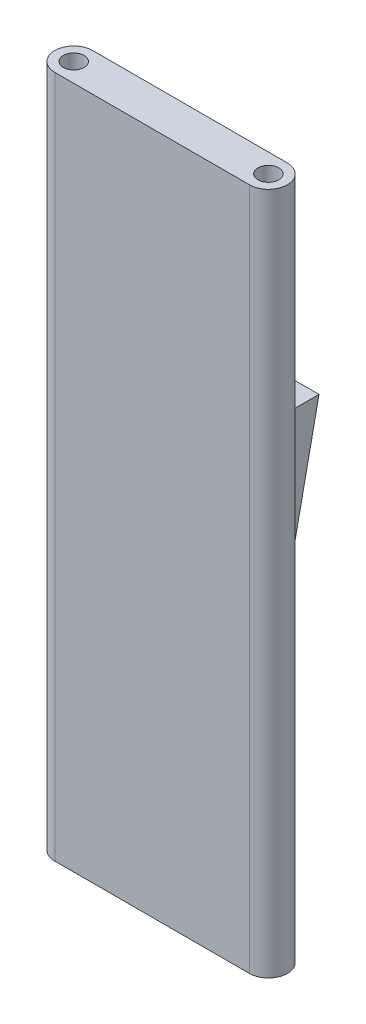
SolidWorks part; units mm, degrees
ref_plane "Front Plane" through (0, 0, 0) normal (0, 0, 1) x (1, 0, 0)
ref_plane "Top Plane" through (0, 0, 0) normal (0, 1, 0) x (1, 0, 0)
ref_plane "Right Plane" through (0, 0, 0) normal (1, 0, 0) x (0, 0, -1)
sketch "Sketch1" plane through (0, 0, 0) normal (0, 1, 0) x (1, 0, 0)
  line L0 (-28.5, 0) -> (28.5, 0) construction
  line L1 (-28.5, 0) -> (28.5, 0) construction
  line L2 (-28.5, 5.55) -> (28.5, 5.55)
  line L3 (-28.5, -5.55) -> (28.5, -5.55)
  circle A0 centre (-28.5, 0) radius 3.05
  circle A1 centre (28.5, 0) radius 3.05
  arc A2 (-28.5, 5.55) -> (-28.5, -5.55) centre (-28.5, 0) ccw
  arc A3 (28.5, -5.55) -> (28.5, 5.55) centre (28.5, 0) ccw
  point P4 (0, 0)
  dimension "D1" = 6.1
  dimension "D2" = 2.5
  dimension "D3" = 57
extrude "Boss-Extrude1" add sketch "Sketch1" along normal mid plane 200
sketch "Sketch2" plane through (0, 0, 0) normal (1, 0, 0) x (0, 0, -1)
  line L0 (5.55, 36.6649) -> (5.55, -0.5321)
  line L1 (5.55, 100) -> (5.55, -100) construction
  line L2 (5.55, -0.5321) -> (7.05, -0.5321)
  line L3 (7.05, -0.5321) -> (14.8208, 36.6649)
  line L4 (14.8208, 36.6649) -> (5.55, 36.6649)
  dimension "D1" = 11.8
  dimension "D2" = 38
  dimension "D3" = 1.5
extrude "Boss-Extrude2" add sketch "Sketch2" along normal up to vertex (28.5 mm away) and the other way up to vertex (28.5 mm away) up to point (28.5, 100, -5.55) other way up to point (-28.5, 100, -5.55)
sketch "Sketch3" plane through (0, -1.4335, -6.8617) normal (0, -0.2045, -0.9789) x (-1, 0, 0)
  line L0 (-14, 33.9209) -> (14, 5.9209) construction
  line L1 (0, 11.204) -> (0, -11.204) construction
  line L3 (-28.5, 0.9209) -> (-28.5, 38.9209) construction
  circle A0 centre (-14, 33.9209) radius 1.5
  circle A1 centre (-14, 5.9209) radius 1.5
  circle A2 centre (14, 33.9209) radius 1.5
  circle A3 centre (14, 5.9209) radius 1.5
  circle A4 centre (-14, 33.9209) radius 2.5
  circle A5 centre (14, 33.9209) radius 2.5
  circle A6 centre (14, 5.9209) radius 2.5
  circle A7 centre (-14, 5.9209) radius 2.5
  point P8 (0, 19.9209)
  point P13 (-28.5, 19.9209)
  dimension "D1" = 3
  dimension "D2" = 28
  dimension "D3" = 28
  dimension "D4" = 1
extrude "Boss-Extrude3" add sketch "Sketch3" along normal blind 1.5
chamfer "Chamfer1" distance 0.5 angle 45 4 edges at (14, 6.5027, -10.052) (-14, 6.5027, -10.052) (-14, 33.911, -15.7779) (14, 33.911, -15.7779)
